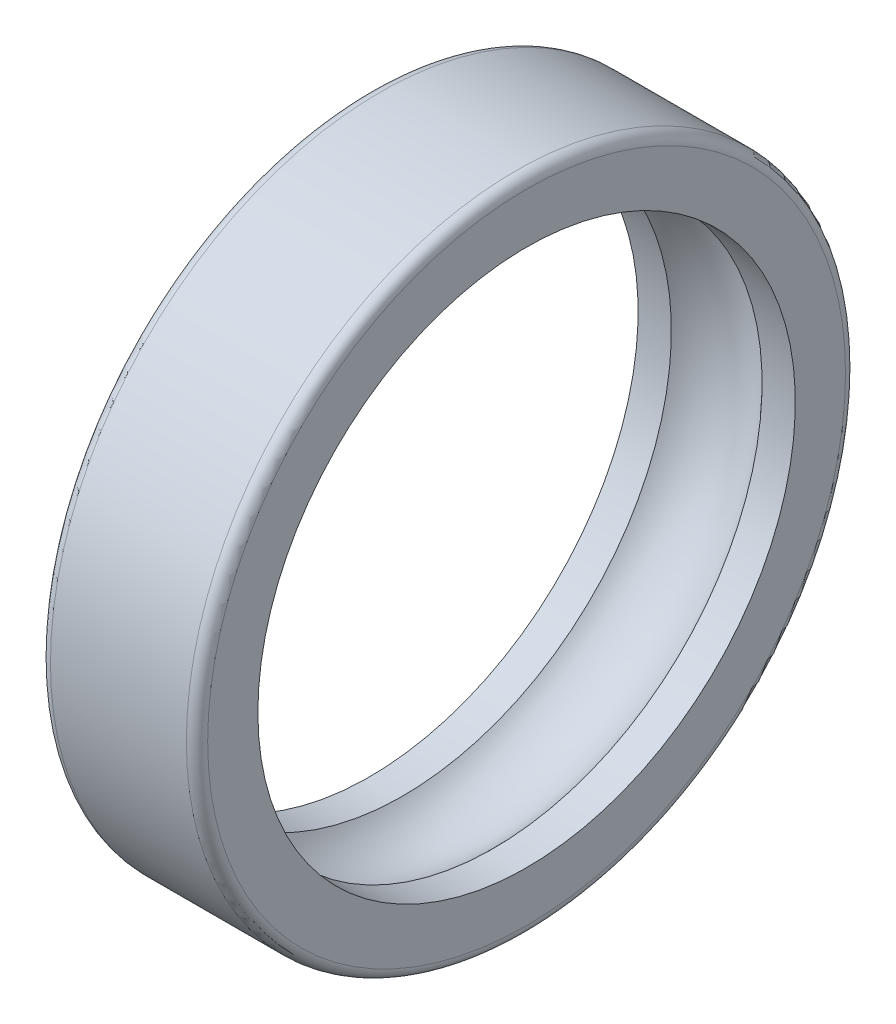
SolidWorks part; units mm, degrees
ref_plane "Front Plane" through (0, 0, 0) normal (0, 0, 1) x (1, 0, 0)
ref_plane "Top Plane" through (0, 0, 0) normal (0, 1, 0) x (1, 0, 0)
ref_plane "Right Plane" through (0, 0, 0) normal (1, 0, 0) x (0, 0, -1)
sketch "Sketch1" plane through (0, 0, 0) normal (0, 0, 1) x (1, 0, 0)
  line L0 (-25.3585, 0) -> (48.5277, 0) construction
  line L1 (0, 0) -> (0, 53) construction
  line L2 (-15.5, 65) -> (15.5, 65)
  line L3 (-15.5, 65) -> (-15.5, 53)
  line L4 (-15.5, 53) -> (-8.9443, 53)
  line L5 (15.5, 65) -> (15.5, 53)
  line L6 (-15.5, 65) -> (15.5, 53) construction
  line L7 (-15.5, 53) -> (15.5, 65) construction
  line L8 (8.9443, 53) -> (15.5, 53)
  arc A0 (-8.9443, 53) -> (8.9443, 53) centre (0, 45) cw
  point P3 (0, 59)
  dimension "D4" = 12
  dimension "D1" = 31
  dimension "D2" = 53
  dimension "D3" = 65
  dimension "D5" = 8
revolve "Revolve1" add sketch "Sketch1" angle 360 about L0
fillet "Fillet1" radius 2.1 2 edges at (15.5, 0, 65) (-15.5, 0, 65)
scale "Scale1" scale about centroid uniform scaling yes scale factor 0.07
